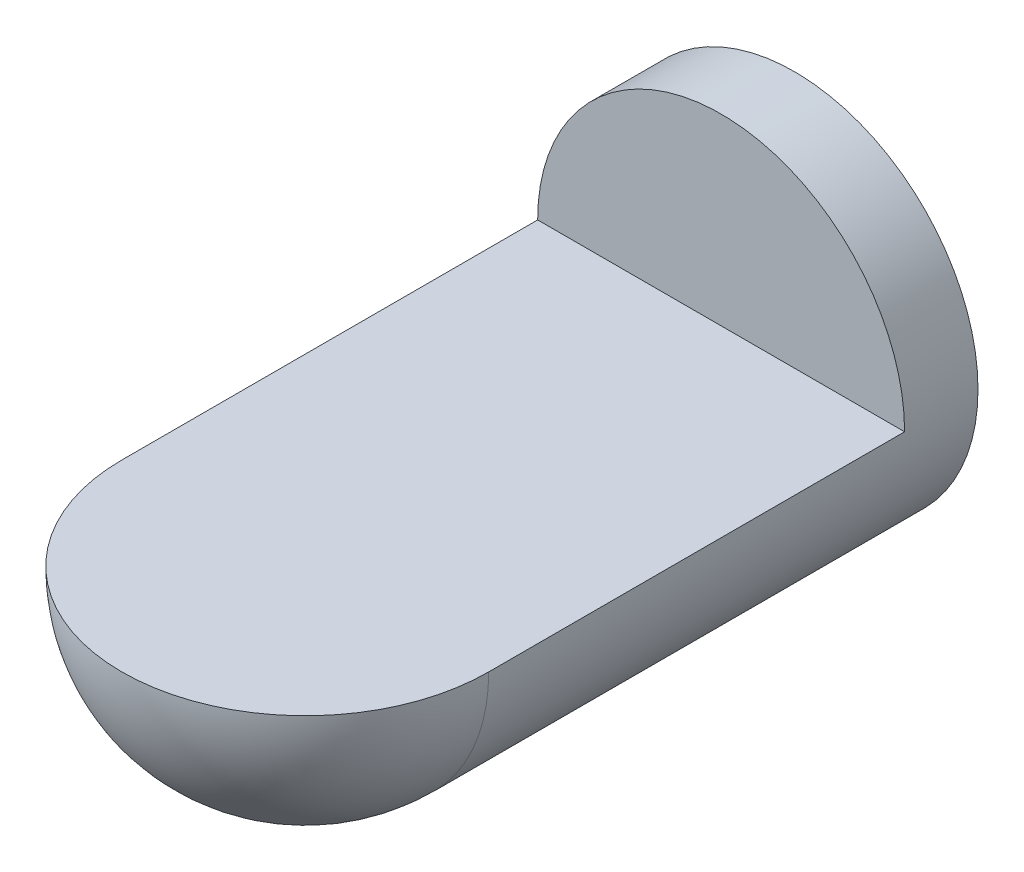
SolidWorks part; units mm, degrees
ref_plane "Front Plane" through (0, 0, 0) normal (0, 0, 1) x (1, 0, 0)
ref_plane "Top Plane" through (0, 0, 0) normal (0, 1, 0) x (1, 0, 0)
ref_plane "Right Plane" through (0, 0, 0) normal (1, 0, 0) x (0, 0, -1)
sketch "Sketch1" plane through (0, 0, 0) normal (1, 0, 0) x (0, 0, -1)
  line L0 (-146.9091, 0) -> (313.5945, 0) construction
  line L1 (200, 0) -> (-75, 0)
  line L2 (200, 0) -> (200, 75)
  line L3 (0, 75) -> (200, 75)
  arc A0 (-75, 0) -> (0, 75) centre (0, 0) cw
  dimension "D1" = 75
  dimension "D2" = 200
revolve "Revolve1" add sketch "Sketch1" angle 360 about L0
sketch "Sketch2" plane through (0, 0, 0) normal (1, 0, 0) x (0, 0, -1)
  line L0 (-88.0407, 0) -> (120.4455, 0) construction
  line L1 (170, 0) -> (170, 75)
  line L2 (200, 75) -> (0, 75) construction
  line L3 (170, 0) -> (-75, 0)
  line L4 (170, 75) -> (0, 75)
  line L5 (200, -75) -> (200, 75) construction
  arc A0 (0, 75) -> (0, -75) centre (0, 0) ccw construction
  arc A1 (-75, 0) -> (0, 75) centre (0, 0) cw
  dimension "D1" = 30
extrude "Cut-Extrude1" cut sketch "Sketch2" along normal through all and the other way through all
ref_axis "Axis1" through (0, 82.5, 0) along (0, -1, 0)
equation "\"link5_diameter\"=150"
equation "\"D1@Sketch1\"=\"link5_diameter\"/2"
equation "\"link5_length\"=200"
equation "\"D2@Sketch1\"=\"link5_length\""
equation "\"base_link_length\"=150"
equation "\"link1_diameter\"=150"
equation "\"link1_length\"=150"
equation "\"link2_diameter\"=150"
equation "\"link2_length\"=300"
equation "\"link3_diameter\"=150"
equation "\"link3_length\"=150"
equation "\"link4_diameter\"=150"
equation "\"link4_length\"=150"
equation "\"end_effector_diameter\"=150"
equation "\"end_effector_length\"=150"
equation "\"base_link_diameterA\"=200"
equation "\"base_link_diameterB\"=150"
equation "\"base_link_lengthA\"=50"
equation "\"base_link_diameter\"=75"
